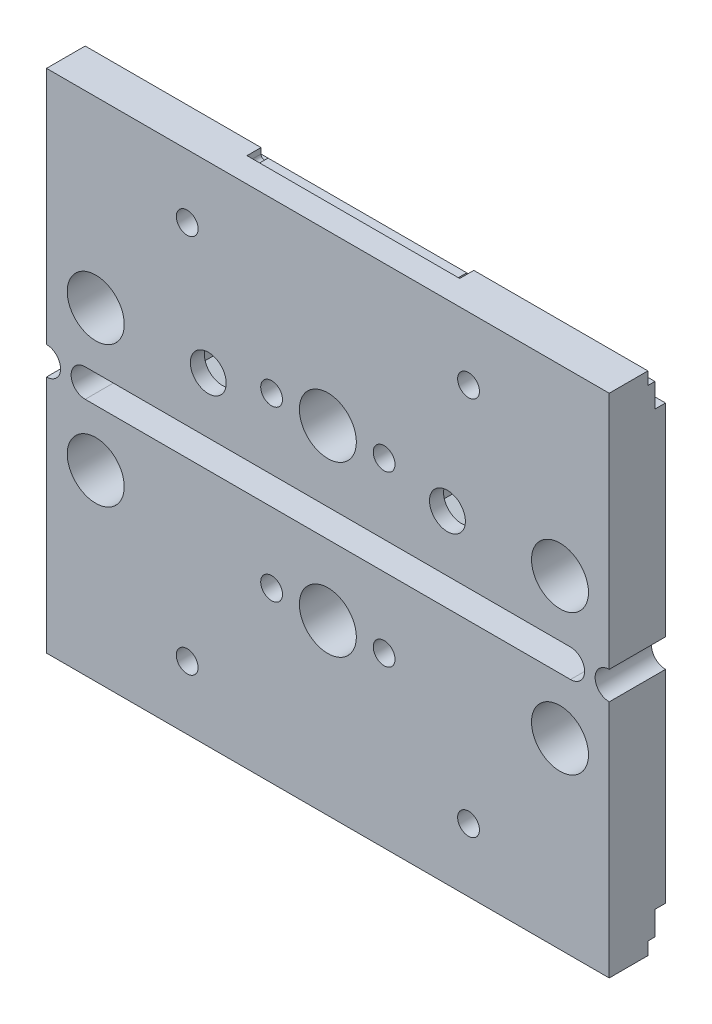
SolidWorks part; units mm, degrees
ref_plane "前视基准面" through (0, 0, 0) normal (0, 0, 1) x (1, 0, 0)
ref_plane "上视基准面" through (0, 0, 0) normal (0, 1, 0) x (1, 0, 0)
ref_plane "右视基准面" through (0, 0, 0) normal (1, 0, 0) x (0, 0, -1)
sketch "前视图草图" plane through (0, 0, 0) normal (0, 0, 1) x (1, 0, 0)
  line L0 (0, 0) -> (8.5179, 0) construction
  line L1 (0, 0) -> (0, 5.4227) construction
sketch "草图2" plane through (0, 0, 0) normal (0, 0, 1) x (1, 0, 0)
  line L0 (0, 0) -> (80, 0)
  line L1 (-200000, 0) -> (200008.5179, 0) construction
  line L2 (80, 0) -> (80, 34)
  line L3 (80, 34) -> (0, 34)
  line L4 (0, -200000) -> (0, 200005.4227) construction
  line L5 (0, 34) -> (0, 0)
  circle A0 centre (7, 8) radius 4.05
  circle A1 centre (40, 10) radius 4.05
  circle A2 centre (73, 8) radius 4.05
  dimension "D3" = 8
  dimension "D5" = 10
  dimension "D9" = 8.1
  dimension "D10" = 8.1
  dimension "D11" = 8.1
  dimension "D1" = 34
  dimension "D2" = 80
  dimension "D4" = 7
  dimension "D6" = 7
  dimension "D7" = 8
  dimension "D8" = 40
extrude "凸台-拉伸1" add sketch "草图2" along normal blind 8
sketch "草图3" plane through (0, 0, 8) normal (0, 0, 1) x (1, 0, 0)
  line L0 (16.088, 8) -> (31.4805, 8) construction
  line L1 (7, 8) -> (7, 16.8386) construction
  line L2 (73, 8) -> (73, 16.5917) construction
  line L4 (-200000, 0) -> (200008.5179, 0) construction
  circle A2 centre (23, 8) radius 2.55
  circle A3 centre (57, 8) radius 2.55
  dimension "D4" = 5.1
  dimension "D5" = 5.1
  dimension "D1" = 8
  dimension "D2" = 16
  dimension "D3" = 16
extrude "切除-拉伸1" cut sketch "草图3" against normal through all
sketch "草图4" plane through (80, 0, 0) normal (1, 0, 0) x (0, 0, -1)
  line L1 (0, -200000) -> (0, 200005.4227) construction
  line L2 (-1.5, 32.2) -> (-2.5, 32.2)
  line L3 (-2.5, 32.2) -> (-2.5, 34)
  line L4 (-8, 34) -> (0, 34) construction
  line L5 (-2.5, 34) -> (0, 34)
  line L6 (-1.5, 32.2) -> (-1.5, 28.8)
  line L7 (-1.5, 28.8) -> (0, 28.8)
  line L8 (0, 28.8) -> (0, 34)
  dimension "D1" = 3.4
  dimension "D2" = 2.5
  dimension "D3" = 1.5
  dimension "D4" = 1.8
extrude "切除-拉伸2" cut sketch "草图4" against normal through all
sketch "草图5" plane through (0, 0, 8) normal (0, 0, 1) x (1, 0, 0)
  line L0 (40, 10) -> (56.5376, 10) construction
  circle A0 centre (40, 10) radius 8 construction
  circle A1 centre (48, 10) radius 1.55
  circle A2 centre (32, 10) radius 1.55
  dimension "D1" = 3.1
  dimension "D2" = 3.1
  dimension "D3" = 16
extrude "切除-拉伸3" cut sketch "草图5" against normal through all
sketch "草图7" plane through (0, 0, 0) normal (0, 0, -1) x (-1, 0, 0)
  line L0 (-80, 0) -> (-80, 28.8) construction
  line L1 (-52.9, 5.6329) -> (-52.9, 10.3671)
  line L14 (-52.9, 10.3671) -> (-57, 12.7343)
  line L15 (-57, 12.7343) -> (-61.1, 10.3671)
  line L19 (-61.1, 10.3671) -> (-61.1, 5.6329)
  line L20 (-61.1, 5.6329) -> (-57, 3.2657)
  line L21 (-57, 3.2657) -> (-52.9, 5.6329)
  line L22 (-27.1, 5.6329) -> (-23, 3.2657)
  line L23 (-23, 3.2657) -> (-18.9, 5.6329)
  line L24 (-18.9, 5.6329) -> (-18.9, 10.3671)
  line L25 (-18.9, 10.3671) -> (-23, 12.7343)
  line L26 (-23, 12.7343) -> (-27.1, 10.3671)
  line L27 (-27.1, 10.3671) -> (-27.1, 5.6329)
  circle A6 centre (-57, 8) radius 4.1 construction
  circle A10 centre (-23, 8) radius 4.1 construction
  dimension "D1" = 8.2
extrude "切除-拉伸4" cut sketch "草图7" against normal blind 6
sketch "草图8" plane through (0, 0, 0) normal (0, 0, -1) x (-1, 0, 0)
  line L0 (-80, 0) -> (-80, 28.8) construction
  line L1 (-48, 6.7091) -> (-45.15, 8.3546)
  line L5 (-45.15, 8.3546) -> (-45.15, 11.6454)
  line L6 (-45.15, 11.6454) -> (-48, 13.2909)
  line L7 (-48, 13.2909) -> (-50.85, 11.6454)
  line L8 (-50.85, 11.6454) -> (-50.85, 8.3546)
  line L9 (-50.85, 8.3546) -> (-48, 6.7091)
  line L10 (-32, 6.7091) -> (-29.15, 8.3546)
  line L11 (-29.15, 8.3546) -> (-29.15, 11.6454)
  line L12 (-29.15, 11.6454) -> (-32, 13.2909)
  line L13 (-32, 13.2909) -> (-34.85, 11.6454)
  line L14 (-34.85, 11.6454) -> (-34.85, 8.3546)
  line L15 (-34.85, 8.3546) -> (-32, 6.7091)
  circle A2 centre (-48, 10) radius 2.85 construction
  circle A3 centre (-32, 10) radius 2.85 construction
  dimension "D1" = 5.7
extrude "切除-拉伸5" cut sketch "草图8" against normal blind 4.5
sketch "草图20" plane through (0, 0, 0) normal (0, 0, -1) x (-1, 0, 0)
  circle A0 centre (-40, 10) radius 5.5
  dimension "D1" = 11
sketch "草图25" plane through (0, 0, 0) normal (0, 0, -1) x (-1, 0, 0)
  line L0 (-51.4471, 25) -> (-40.1512, 25) construction
  line L1 (-60, 37.1428) -> (-60, 21.9179) construction
  line L2 (-20, 37.1428) -> (-20, 21.9179) construction
  line L3 (0, 34) -> (-80, 34) construction
  line L4 (-80, 0) -> (-80, 28.8) construction
  line L5 (0, -200000) -> (0, 200005.4227) construction
  circle A0 centre (-60, 25) radius 1.55
  circle A1 centre (-20, 25) radius 1.55
  dimension "D4" = 3.1
  dimension "D5" = 3.1
  dimension "D1" = 9
  dimension "D2" = 20
  dimension "D3" = 20
extrude "切除-拉伸13" cut sketch "草图25" against normal through all
sketch "草图19" plane through (0, 0, 2.5) normal (0, 0, -1) x (-1, 0, 0)
  line L0 (0, 34) -> (-80, 34) construction
  line L1 (-25, 34) -> (-55.2479, 34)
  line L2 (-25, 34) -> (-25, 33.2)
  line L3 (-26, 33.2) -> (-54.2479, 33.2)
  line L4 (-55.2479, 34) -> (-55.2479, 33.2)
  line L5 (0, -200000) -> (0, 200005.4227) construction
  line L7 (0, 32.2) -> (-80, 32.2) construction
  line L8 (-56.3335, 32.7) -> (-52.9089, 32.7) construction
  line L9 (-55.2479, 1028.5823) -> (-55.2479, 33.2) construction
  line L10 (-25, 1028.5823) -> (-25, 32.7) construction
  line L11 (-55.2479, 32.7) -> (-55.2479, -973.3) construction
  line L12 (-25, 32.7) -> (-25, -973.3) construction
  arc A3 (-55.2479, 33.2) -> (-54.2479, 33.2) centre (-54.7479, 33.2) ccw
  arc A6 (-26, 33.2) -> (-25, 33.2) centre (-25.5, 33.2) ccw
  dimension "D3" = 1
  dimension "D4" = 1
  dimension "D2" = 0.8
  dimension "D1" = 0.5
  dimension "D9" = 25
extrude "切除-拉伸11" cut sketch "草图19" against normal blind 2
sketch "草图22" plane through (0, 0, 8) normal (0, 0, 1) x (1, 0, 0)
  line L1 (0, -200000) -> (0, 200005.4227) construction
  line L2 (0, -4) -> (5.5, -4)
  line L4 (80, 0) -> (74.5, 0)
  line L5 (3.5, 1.9875) -> (3.5, -4.1402) construction
  line L6 (76.5, -11.5647) -> (76.5, -5.1636) construction
  line L7 (80, 0) -> (80, 34) construction
  line L8 (74.5, -4) -> (80, -4)
  line L9 (5.5, 0) -> (0, 0)
  line L10 (78, -2.9635) -> (78, -4.3032) construction
  line L11 (2, -8.393) -> (2, -15.1693) construction
  arc A0 (5.5, 0) -> (5.5, -4) centre (5.5, -2) ccw
  arc A1 (74.5, -4) -> (74.5, 0) centre (74.5, -2) ccw
  arc A2 (0, -4) -> (0, 0) centre (0, -2) ccw
  arc A3 (80, 0) -> (80, -4) centre (80, -2) ccw
  dimension "D1" = 3.5
  dimension "D2" = 3.5
  dimension "D3" = 4
  dimension "D4" = 2
  dimension "D5" = 2
extrude "凸台-拉伸2" add sketch "草图22" against normal blind 8
ref_plane "基准面1" through (0, -2, 0) normal (0, -1, 0) x (-1, 0, 0)
mirror "镜向2" about plane through (0, -2, 0) normal (0, -1, 0) of "切除-拉伸3", "凸台-拉伸1", "切除-拉伸2", "切除-拉伸5", "切除-拉伸11", "切除-拉伸13"
sketch "草图23" plane through (0, 0, 0) normal (0, 0, -1) x (-1, 0, 0)
  line L0 (-80, 0) -> (0, 0)
  line L1 (0, 0) -> (0, -4)
  line L2 (0, -4) -> (-80, -4)
  line L3 (-80, -4) -> (-80, 0)
sketch "草图24" plane through (0, 0, 8) normal (0, 0, 1) x (1, 0, 0)
  line L0 (80, -4) -> (80, 0)
  line L1 (80, 0) -> (0, 0)
  line L2 (0, 0) -> (0, -4)
  line L3 (0, -4) -> (80, -4)
